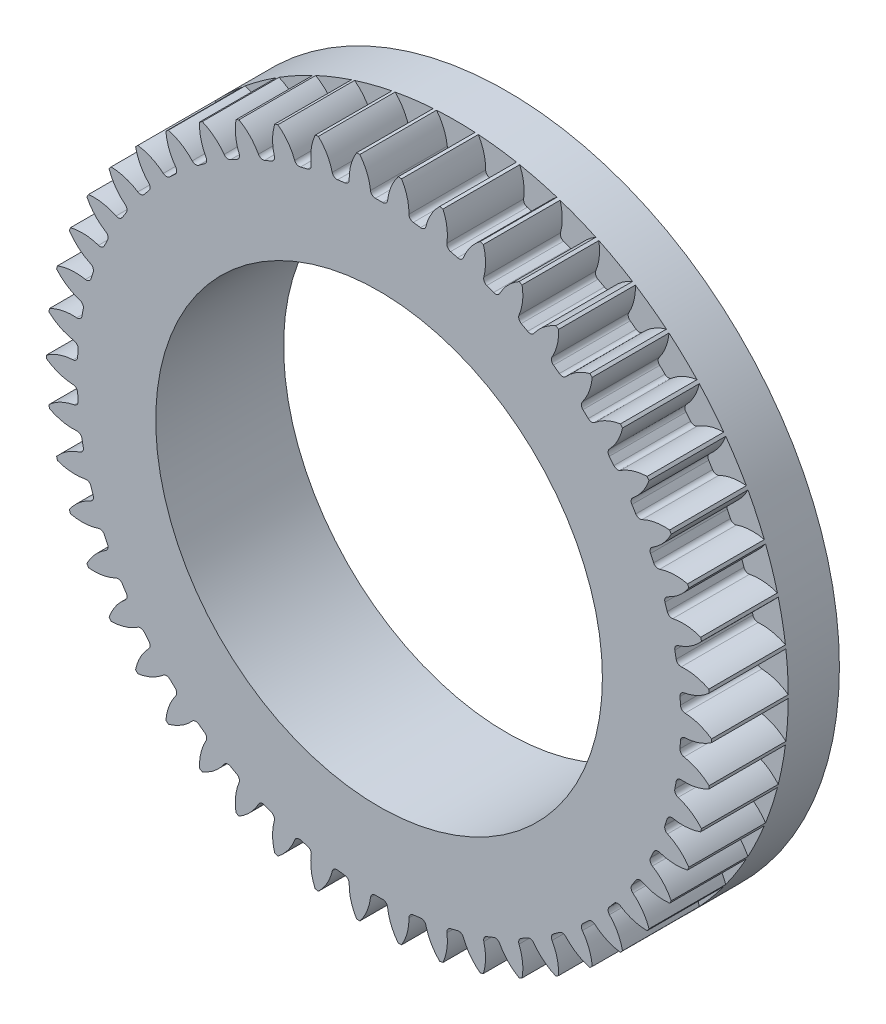
SolidWorks part; units mm, degrees
ref_plane "Front Plane" through (0, 0, 0) normal (0, 0, 1) x (1, 0, 0)
ref_plane "Top Plane" through (0, 0, 0) normal (0, 1, 0) x (1, 0, 0)
ref_plane "Right Plane" through (0, 0, 0) normal (1, 0, 0) x (0, 0, -1)
sketch "Sketch1" plane through (0, 0, 0) normal (0, 0, 1) x (1, 0, 0)
  line L0 (0, 0) -> (-18.1989, 0) construction
  line L1 (0, 0) -> (0, 8.2854) construction
  circle A0 centre (0, 0) radius 17.465
  circle A1 centre (0, 0) radius 26
  point P19 (0, 0)
  dimension "D1" = 34.93
  dimension "D2" = 52
extrude "Boss-Extrude1" add sketch "Sketch1" along normal blind 10
sketch "Sketch2" plane through (0, 0, 10) normal (0, 0, 1) x (1, 0, 0)
  line L0 (0, 0) -> (0, 26) construction
  line L1 (-0.6432, 23.5912) -> (0, 0) construction
  line L2 (0, 22.4212) -> (0.5017, 21.0429) construction
  circle A0 centre (0, 0) radius 26 construction
  arc A1 (0.6432, 23.5912) -> (-0.6432, 23.5912) centre (0, 0) ccw
  arc A2 (0.9352, 24.9825) -> (-0.9352, 24.9825) centre (0, 0) ccw construction
  arc A3 (-1.5041, 25.9565) -> (-0.6432, 23.5912) centre (-4.6208, 23.4828) cw
  arc A4 (1.5041, 25.9565) -> (0.6432, 23.5912) centre (4.6208, 23.4828) ccw
  point P16 (-0.8817, 24.8437)
  dimension "D1" = 50
  dimension "D2" = 2.4
  dimension "D3" = 20
  dimension "D4" = 1.8708
extrude "Cut-Extrude3" cut sketch "Sketch2" against normal blind 10 and the other way through all flip side to cut
fillet "Fillet1" radius 0.38 2 edges at (0.6432, 23.5912, 5) (-0.6432, 23.5912, 5)
pattern_circular "CirPattern1" count 50 over 360 about axis through (0, 0, 10) along (0, 0, 1) of "Cut-Extrude3", "Fillet1"
sketch "Sketch5" plane through (0, 0, 10) normal (0, 0, 1) x (1, 0, 0)
  line L0 (0, 17.465) -> (0, 32.465) construction
  circle A0 centre (0, 0) radius 17.465 construction
  circle A1 centre (0, 32.465) radius 1.5
  dimension "D2" = 3
  dimension "D1" = 15
sketch "Sketch6" plane through (0, 0, 0) normal (0, 0, 1) x (1, 0, 0)
  line L0 (0, 0) -> (-20.4531, 0) construction
  circle A0 centre (0, 0) radius 25
  dimension "D1" = 50
extrude "Cut-Extrude4" cut sketch "Sketch1<8>" along normal blind 4
sketch "Sketch1<8>" plane through (0, 0, 0) normal (0, 0, 1) x (1, 0, 0) same geometry as "Sketch1"
extrude "Boss-Extrude2" add sketch "Sketch1<9>" along normal blind 4
sketch "Sketch1<9>" plane through (0, 0, 0) normal (0, 0, 1) x (1, 0, 0) same geometry as "Sketch1"
equation "\"No. of teeth\"= 50"
equation "\"Module\"= 1mm"
equation "\"Bore Diameter\"= 34.93mm"
equation "\"Pressure Angle\"= 20"
equation "\"Outer Diameter\"= ( \"No. of teeth\" + 2 ) * \"Module\""
equation "\"Pitch Diameter\"= \"No. of teeth\" * \"Module\""
equation "\"Backlash\"= 0.3 * \"Module\""
equation "\"Are Length\"= ( ( \"Module\" * pi ) / 2 ) + \"Backlash\""
equation "\"Fillet Radius\"= 0.38 * \"Module\""
equation "\"Tooth Depth\"= IIF ( \"Module\" <= 1.25 , \"Module\" * 2.4 , \"Module\" * 2.25 )"
equation "\"D1@Sketch1\"=\"Bore Diameter\""
equation "\"D1@Sketch2\"=\"Pitch Diameter\""
equation "\"D2@Sketch2\"=\"Tooth Depth\""
equation "\"D3@Sketch2\"=\"Pressure Angle\""
equation "\"D4@Sketch2\"=\"Are Length\""
equation "\"D1@Fillet1\"=\"Fillet Radius\""
equation "\"D1@CirPattern1\"=\"No. of teeth\""
equation "\"D1@Sketch6\"=\"Pitch Diameter\""
